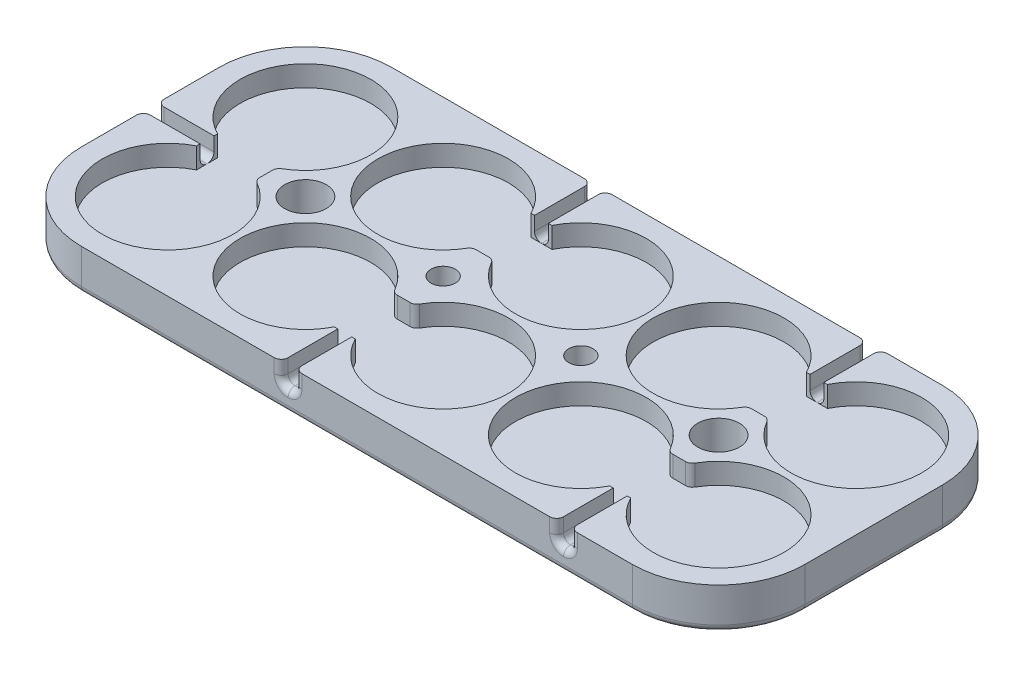
SolidWorks part; units mm, degrees
ref_plane "Front Plane" through (0, 0, 0) normal (0, 0, 1) x (1, 0, 0)
ref_plane "Top Plane" through (0, 0, 0) normal (0, 1, 0) x (1, 0, 0)
ref_plane "Right Plane" through (0, 0, 0) normal (1, 0, 0) x (0, 0, -1)
sketch "Sketch2" plane through (0, 0, 0) normal (0, 1, 0) x (1, 0, 0)
  line L0 (-39.7, 9.925) -> (-19.85, 9.925) construction
  line L1 (-19.85, 9.925) -> (0, 9.925) construction
  line L2 (0, 9.925) -> (19.85, 9.925) construction
  line L3 (19.85, 9.925) -> (39.7, 9.925) construction
  line L4 (39.7, 9.925) -> (39.7, -9.925) construction
  line L5 (39.7, -9.925) -> (19.85, -9.925) construction
  line L6 (19.85, -9.925) -> (0, -9.925) construction
  line L7 (0, -9.925) -> (-19.85, -9.925) construction
  line L8 (-39.7, 9.925) -> (-39.7, -9.925) construction
  line L9 (-39.7, -9.925) -> (-19.85, -9.925) construction
  line L10 (-39.7, 9.925) -> (39.7, -9.925) construction
  line L11 (-30.275, 9.925) -> (-29.275, 9.925) construction
  line L16 (-39.7, 0.5) -> (-39.7, -0.5) construction
  line L17 (-39.7, 22.35) -> (39.7, 22.35)
  line L19 (52.125, -9.925) -> (52.125, 9.925)
  line L20 (39.7, -22.35) -> (-39.7, -22.35)
  line L21 (-52.125, -9.925) -> (-52.125, 9.925)
  line L22 (-39.7, -9.925) -> (-52.125, -9.925) construction
  circle A0 centre (-39.7, 9.925) radius 9.425
  circle A1 centre (-19.85, 9.925) radius 9.425
  circle A2 centre (-39.7, -9.925) radius 9.425
  circle A3 centre (-19.85, -9.925) radius 9.425
  circle A4 centre (0, 9.925) radius 9.425
  circle A5 centre (0, -9.925) radius 9.425
  circle A6 centre (19.85, 9.925) radius 9.425
  circle A7 centre (19.85, -9.925) radius 9.425
  circle A8 centre (39.7, 9.925) radius 9.425
  circle A9 centre (39.7, -9.925) radius 9.425
  circle A10 centre (-39.7, 9.925) radius 12.425
  circle A11 centre (-39.7, -9.925) radius 12.425
  circle A12 centre (39.7, -9.925) radius 12.425
  circle A13 centre (39.7, 9.925) radius 12.425
  dimension "D1" = 18.85
  dimension "D2" = 1
  dimension "D3" = 1
  dimension "D4" = 3
extrude "Boss-Extrude1" add sketch "Sketch2" along normal blind 3 contours A13 L17 A10 A1 A11 A3 L20 A12 A7 A6 A5 A4 | A12 A13 A6 A8 | A13 A9 A12 A7 | A13 A12 L19 | A9 A13 A12 A8 | A11 A10 L21 | A11 A10 A1 A0 | A3 A11 A10 A2 | A10 A11 A0 A2 region at (-32.8744, 0, -19.9125) region at (0, 0, 0) region at (48.2539, 0, -18.4789) region at (-50.7094, 0, 0) region at (50.7094, 0, 0) region at (-50.5254, 0, 4.5259) region at (-39.7, 0, 0) region at (48.2539, 0, 18.4789) region at (39.7, 0, 0)
sketch "Sketch3" plane through (0, 0, 0) normal (0, 1, 0) x (1, 0, 0)
  line L0 (52.125, -9.925) -> (52.125, 9.925) construction
  line L1 (-52.125, -22.35) -> (52.125, -22.35)
  line L2 (-52.125, -22.35) -> (-52.125, 22.35)
  line L3 (-52.125, 22.35) -> (52.125, 22.35)
  line L4 (52.125, -22.35) -> (52.125, 22.35)
  line L5 (-52.125, -9.925) -> (-52.125, 9.925) construction
  line L6 (39.7, -22.35) -> (-39.7, -22.35) construction
  line L7 (-39.7, 22.35) -> (39.7, 22.35) construction
  circle A0 centre (-39.7, -9.925) radius 12.425
  circle A1 centre (-39.7, 9.925) radius 12.425
  circle A2 centre (39.7, 9.925) radius 12.425
  circle A3 centre (39.7, -9.925) radius 12.425
  circle A4 centre (-39.7, 9.925) radius 9.425 construction
  arc A5 (-39.7, 22.35) -> (-52.125, 9.925) centre (-39.7, 9.925) ccw construction
  arc A6 (-52.125, -9.925) -> (-39.7, -22.35) centre (-39.7, -9.925) ccw construction
  arc A7 (39.7, -22.35) -> (52.125, -9.925) centre (39.7, -9.925) ccw construction
  arc A8 (52.125, 9.925) -> (39.7, 22.35) centre (39.7, 9.925) ccw construction
extrude "Boss-Extrude2" add sketch "Sketch3" against normal blind 3 contours A3 A2 L3 A1 A0 L1 | A1 A0 | A0 A1 | A0 A1 | A1 L2 A0 | A3 A2 | A2 A3 | A3 A2 | A3 L4 A2 region at (0, 0, 0) region at (-39.7, 0, 11.0895) region at (-50.7094, 0, 0) region at (39.7, 0, 11.0895) region at (-39.7, 0, -11.0895) region at (-39.7, 0, 0) region at (39.7, 0, 0) region at (39.7, 0, -11.0895) region at (50.7094, 0, 0)
sketch "Sketch4" plane through (0, 0, 0) normal (0, 1, 0) x (1, 0, 0)
  line L1 (39.7, -5.675) -> (19.85, -5.675)
  line L2 (39.7, -5.675) -> (39.7, -14.175)
  line L3 (39.7, -14.175) -> (19.85, -14.175)
  line L4 (19.85, -5.675) -> (19.85, -14.175)
  line L5 (0, -5.675) -> (-19.85, -5.675)
  line L6 (0, -5.675) -> (0, -14.175)
  line L7 (0, -14.175) -> (-19.85, -14.175)
  line L8 (-19.85, -5.675) -> (-19.85, -14.175)
  line L9 (-43.95, -9.925) -> (-35.45, -9.925)
  line L10 (-43.95, -9.925) -> (-43.95, 9.925)
  line L11 (-43.95, 9.925) -> (-35.45, 9.925)
  line L12 (-35.45, -9.925) -> (-35.45, 9.925)
  line L13 (-19.85, 14.175) -> (0, 14.175)
  line L14 (-19.85, 14.175) -> (-19.85, 5.675)
  line L15 (-19.85, 5.675) -> (0, 5.675)
  line L16 (0, 14.175) -> (0, 5.675)
  line L17 (19.85, 14.175) -> (39.7, 14.175)
  line L18 (19.85, 14.175) -> (19.85, 5.675)
  line L19 (19.85, 5.675) -> (39.7, 5.675)
  line L20 (39.7, 14.175) -> (39.7, 5.675)
  circle A0 centre (-39.7, 9.925) radius 9.425 construction
  circle A1 centre (-39.7, -9.925) radius 9.425 construction
  circle A2 centre (-19.85, -9.925) radius 9.425 construction
  circle A3 centre (0, -9.925) radius 9.425 construction
  circle A4 centre (19.85, -9.925) radius 9.425 construction
  circle A5 centre (39.7, -9.925) radius 9.425 construction
  circle A6 centre (39.7, 9.925) radius 9.425 construction
  circle A7 centre (19.85, 9.925) radius 9.425 construction
  circle A8 centre (-19.85, 9.925) radius 9.425 construction
  circle A9 centre (0, 9.925) radius 9.425 construction
  point P20 (-39.7, 9.925)
  point P23 (-39.7, -9.925)
  point P26 (-19.85, -9.925)
  point P29 (0, -9.925)
  point P34 (19.85, -9.925)
  point P35 (39.7, -9.925)
  point P40 (39.7, 9.925)
  point P41 (19.85, 9.925)
  point P46 (-19.85, 9.925)
  point P47 (0, 9.925)
  dimension "D1" = 8.5
extrude "Cut-Extrude1" cut sketch "Sketch4" along normal through all
sketch "Sketch5" plane through (0, 0, 0) normal (0, 1, 0) x (1, 0, 0)
  line L0 (-52.125, -9.925) -> (-52.125, 9.925) construction
  line L1 (-10.925, 10.675) -> (-8.925, 10.675)
  line L2 (-10.925, 10.675) -> (-10.925, 22.35)
  line L3 (-10.925, 22.35) -> (-8.925, 22.35)
  line L4 (-8.925, 10.675) -> (-8.925, 22.35)
  line L5 (28.775, 10.675) -> (30.775, 10.675)
  line L6 (28.775, 10.675) -> (28.775, 22.35)
  line L7 (28.775, 22.35) -> (30.775, 22.35)
  line L8 (30.775, 10.675) -> (30.775, 22.35)
  line L9 (28.775, -10.675) -> (30.775, -10.675)
  line L10 (28.775, -10.675) -> (28.775, -22.35)
  line L11 (28.775, -22.35) -> (30.775, -22.35)
  line L12 (30.775, -10.675) -> (30.775, -22.35)
  line L13 (-10.925, -10.675) -> (-8.925, -10.675)
  line L14 (-10.925, -10.675) -> (-10.925, -22.35)
  line L15 (-10.925, -22.35) -> (-8.925, -22.35)
  line L16 (-8.925, -10.675) -> (-8.925, -22.35)
  line L17 (-40.45, -1) -> (-52.125, -1)
  line L18 (-40.45, -1) -> (-40.45, 1)
  line L19 (-40.45, 1) -> (-52.125, 1)
  line L20 (-52.125, -1) -> (-52.125, 1)
  line L21 (-39.7, 22.35) -> (39.7, 22.35) construction
  line L22 (39.7, -22.35) -> (-39.7, -22.35) construction
  line L23 (-35.45, 0) -> (-40.45, 0) construction
  line L24 (-35.45, -1.5126) -> (-35.45, 1.5126) construction
  line L25 (-9.925, -10.675) -> (-9.925, -5.675) construction
  line L26 (-8.4124, -5.675) -> (-11.4376, -5.675) construction
  line L27 (-9.925, 10.675) -> (-9.925, 5.675) construction
  line L28 (-11.4376, 5.675) -> (-8.4124, 5.675) construction
  line L29 (29.775, -10.675) -> (29.775, -5.675) construction
  line L30 (31.2876, -5.675) -> (28.2624, -5.675) construction
  line L31 (29.775, 10.675) -> (29.775, 5.675) construction
  line L32 (28.2624, 5.675) -> (31.2876, 5.675) construction
  dimension "D1" = 2
  dimension "D2" = 5
extrude "Cut-Extrude2" cut sketch "Sketch5" along normal through all
sketch "Sketch7" plane through (0, 0, 0) normal (0, 1, 0) x (1, 0, 0)
  line L0 (-29.775, 0) -> (-9.925, 0) construction
  line L1 (-9.925, 0) -> (9.925, 0) construction
  line L2 (9.925, 0) -> (29.775, 0) construction
  circle A1 centre (-29.775, 0) radius 3
  circle A2 centre (-9.925, 0) radius 1.75
  circle A3 centre (9.925, 0) radius 1.75
  circle A4 centre (29.775, 0) radius 3
  circle A5 centre (-29.775, 0) radius 4.6111 construction
  arc A6 (-11.4376, -5.675) -> (-11.4376, -14.175) centre (-19.85, -9.925) ccw construction
  arc A7 (-35.45, 1.5126) -> (-43.95, 1.5126) centre (-39.7, 9.925) ccw construction
  dimension "D1" = 6
  dimension "D2" = 3.5
extrude "Cut-Extrude3" cut sketch "Sketch7" along normal through all both and the other way through all
sketch "Sketch8" plane through (0, -3, 0) normal (0, -1, 0) x (1, 0, 0)
  circle A0 centre (9.925, 0) radius 3
  circle A1 centre (-9.925, 0) radius 3
  circle A2 centre (-9.925, 0) radius 1.75 construction
  circle A3 centre (9.925, 0) radius 1.75 construction
  circle A4 centre (29.775, 0) radius 3 construction
extrude "Cut-Extrude4" cut sketch "Sketch8" against normal blind 3.5
fillet "Fillet1" radius 1 35 edges at (28.775, 1.5, 22.35) (30.775, 1.5, 22.35) (-10.925, 1.5, 22.35) (-8.925, 1.5, 22.35) (-52.125, 1.5, 1) (-52.125, 1.5, -1) (-8.925, 1.5, -22.35) (-10.925, 1.5, -22.35) (30.775, 1.5, -22.35) (28.775, 1.5, -22.35) (29.775, 0, 22.35) (28.775, 0, 18.2625) (30.775, 0, 18.2625) (-9.925, 0, 22.35) (-8.925, 0, 18.2625) (-10.925, 0, 18.2625) (-48.0375, 0, 1) (-48.0375, 0, -1) (-52.125, 0, 0) (-9.925, 0, -22.35) (-10.925, 0, -18.2625) (-8.925, 0, -18.2625) (29.775, 0, -22.35) (28.775, 0, -18.2625) (30.775, 0, -18.2625) (28.2624, 1.5, 5.675) (31.2876, 1.5, 5.675) (-8.4124, 1.5, 5.675) (-11.4376, 1.5, 5.675) (-35.45, 1.5, -1.5126) (-35.45, 1.5, 1.5126) (-11.4376, 1.5, -5.675) (-8.4124, 1.5, -5.675) (28.2624, 1.5, -5.675) (31.2876, 1.5, -5.675)
fillet "Fillet2" radius 1 8 edges at (-48.4858, -3, 18.7108) (-52.125, -3, 0) (-48.4858, -3, -18.7108) (0, -3, -22.35) (48.4858, -3, -18.7108) (52.125, -3, 0) (48.4858, -3, 18.7108) (0, -3, 22.35)
sketch "Sketch9" plane through (0, -3, 0) normal (0, -1, 0) x (1, 0, 0)
  line L0 (-48.5919, 6.8) -> (-30.8081, 6.8) construction
  line L2 (-28.7419, 13.05) -> (8.8919, 13.05) construction
  line L4 (10.9581, 13.05) -> (48.5919, 13.05) construction
  line L5 (-48.5919, -13.05) -> (-30.8081, -13.05) construction
  line L6 (-28.7419, -13.05) -> (8.8919, -13.05) construction
  line L8 (10.9581, -13.05) -> (48.5919, -13.05) construction
  line L10 (-48.5919, 13.05) -> (-30.8081, 13.05) construction
  line L11 (-39.7, 13.05) -> (-39.7, 6.8) construction
  line L12 (-48.5919, -6.8) -> (-30.8081, -6.8) construction
  line L13 (-39.7, -6.8) -> (-39.7, -13.05) construction
  line L14 (-42.825, -18.8169) -> (-42.825, 18.8169) construction
  line L15 (-36.575, -18.8169) -> (-36.575, 18.8169) construction
  line L16 (-36.575, 0) -> (-42.825, 0) construction
  line L17 (-39.7, -6.8) -> (-39.7, 0) construction
  circle A0 centre (39.7, 9.925) radius 9.425 construction
  circle A1 centre (19.85, 9.925) radius 9.425 construction
  circle A2 centre (0, 9.925) radius 9.425 construction
  circle A3 centre (-19.85, 9.925) radius 9.425 construction
  circle A4 centre (-39.7, 9.925) radius 9.425 construction
  circle A5 centre (-39.7, -9.925) radius 9.425 construction
  circle A6 centre (-19.85, -9.925) radius 9.425 construction
  circle A7 centre (0, -9.925) radius 9.425 construction
  circle A8 centre (19.85, -9.925) radius 9.425 construction
  circle A9 centre (39.7, -9.925) radius 9.425 construction
  arc A10 (31.5574, 5.1786) -> (31.2876, 14.175) centre (39.7, 9.925) ccw construction
  arc A11 (28.2624, 14.175) -> (27.9926, 5.1786) centre (19.85, 9.925) ccw construction
  arc A12 (-8.1426, 5.1786) -> (-8.4124, 14.175) centre (0, 9.925) ccw construction
  arc A13 (-11.4376, 14.175) -> (-11.7074, 5.1786) centre (-19.85, 9.925) ccw construction
  arc A14 (-34.9536, 1.7824) -> (-43.95, 1.5126) centre (-39.7, 9.925) ccw construction
  arc A15 (-43.95, -1.5126) -> (-34.9536, -1.7824) centre (-39.7, -9.925) ccw construction
  arc A16 (-11.7074, -5.1786) -> (-11.4376, -14.175) centre (-19.85, -9.925) ccw construction
  arc A17 (-8.4124, -14.175) -> (-8.1426, -5.1786) centre (0, -9.925) ccw construction
  arc A18 (27.9926, -5.1786) -> (28.2624, -14.175) centre (19.85, -9.925) ccw construction
  arc A19 (31.2876, -14.175) -> (31.5574, -5.1786) centre (39.7, -9.925) ccw construction
  text T0 "<b>5+</b>" font "Arial Rounded MT Bold" height 6.5
  text T2 "<b>3+</b>" font "Arial Rounded MT Bold" height 6.5
  text T4 "<b>1+</b>" font "Arial Rounded MT Bold" height 6.5
  text T7 "<b>7+</b>" font "Arial Rounded MT Bold" height 6.5
  text T9 "<b>9+</b>" font "Arial Rounded MT Bold" height 6.5
  dimension "D1" = 6.25
  dimension "D2" = 6.25
  dimension "D3" = 6.25
extrude "Cut-Extrude5" cut sketch "Sketch9" against normal blind 0.5
